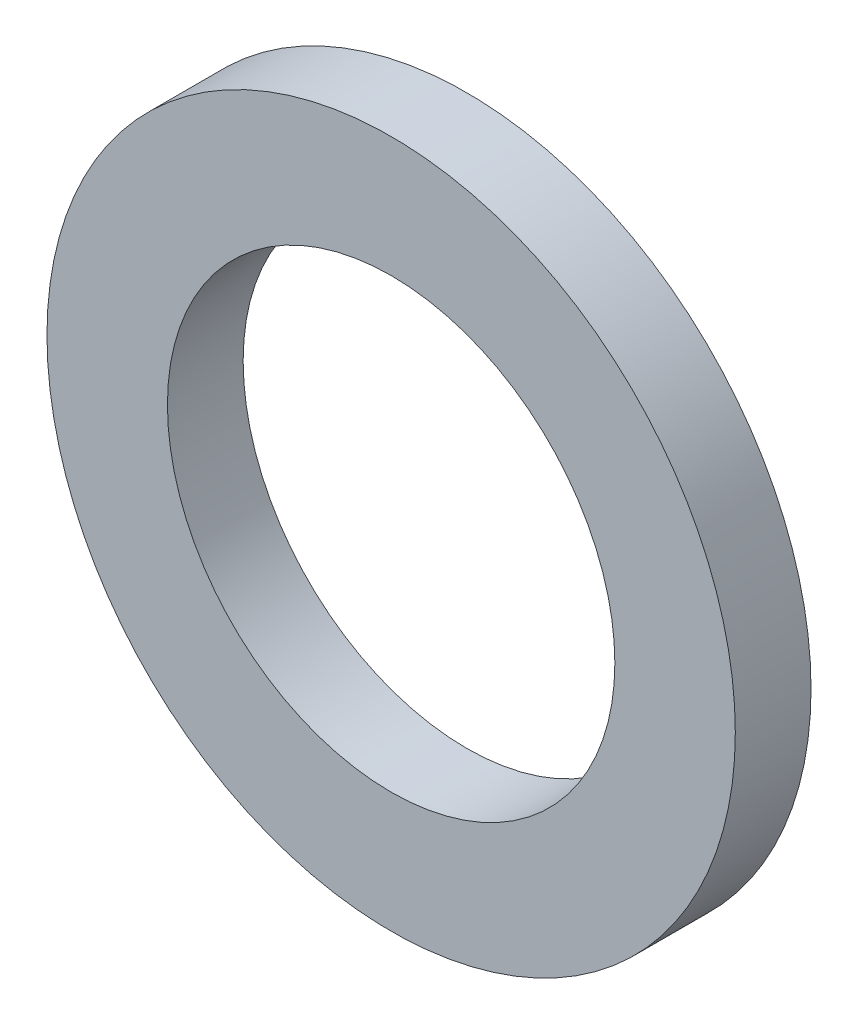
SolidWorks part; units mm, degrees
ref_plane "Front Plane" through (0, 0, 0) normal (0, 0, 1) x (1, 0, 0)
ref_plane "Top Plane" through (0, 0, 0) normal (0, 1, 0) x (1, 0, 0)
ref_plane "Right Plane" through (0, 0, 0) normal (1, 0, 0) x (0, 0, -1)
sketch "Sketch1" plane through (0, 0, 0) normal (0, 0, 1) x (1, 0, 0)
  circle A0 centre (0, 0) radius 10
  circle A1 centre (0, 0) radius 6.5
  dimension "OD" = 20
  dimension "ID1" = 13
extrude "Boss-Extrude1" add sketch "Sketch1" along normal blind 2.2
ref_axis "Center Axis 1" through (0, 0, 2.2) along (0, 0, -1)
ref_plane "Contact Plane 1" through (0, 0, 2.2) normal (0, 0, 1) x (1, 0, 0)
ref_plane "Contact Plane 2" through (0, 0, 0) normal (0, 0, -1) x (-1, 0, 0)
